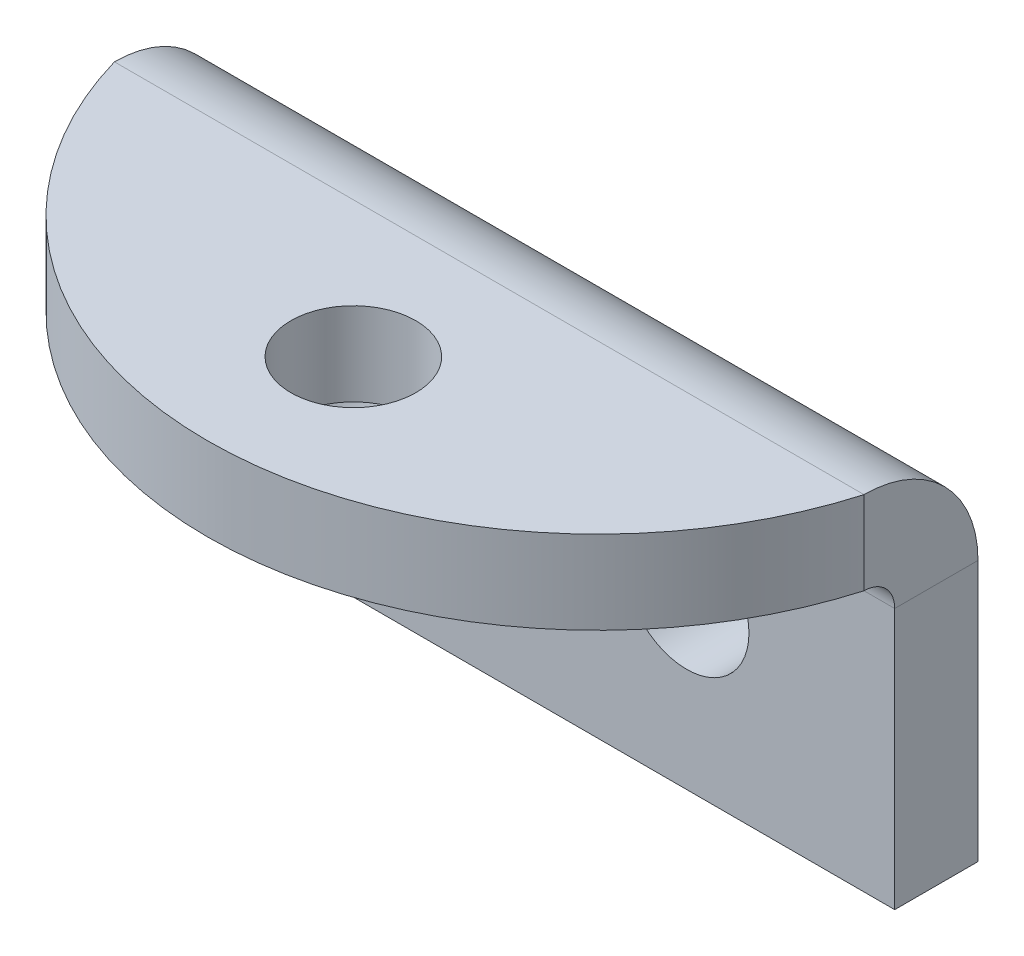
SolidWorks part; units mm, degrees
note: The reader was unsure of these and kept them because the rebuilt part matched: flange length of "边线-法兰1".
material "普通碳钢"
ref_plane "前视" through (0, 0, 0) normal (0, 0, 1) x (1, 0, 0)
ref_plane "上视" through (0, 0, 0) normal (0, 1, 0) x (1, 0, 0)
ref_plane "右视" through (0, 0, 0) normal (1, 0, 0) x (0, 0, -1)
sketch "草图1" plane through (0, 0, 0) normal (0, 0, 1) x (1, 0, 0)
  line L0 (9, 0) -> (9, -9) construction
  line L1 (0, 0) -> (18, 0)
  line L2 (0, 0) -> (0, -9)
  line L3 (0, -9) -> (18, -9)
  line L4 (18, 0) -> (18, -9)
  circle A0 centre (5, -5) radius 1.5
  circle A1 centre (13, -5) radius 1.5
  dimension "D3" = 8
  dimension "D4" = 4
  dimension "D5" = 3
  dimension "D1" = 18
  dimension "D2" = 9
base flange "基体-法兰1" sketch "草图1" thickness 2 reverse thickness direction no parameters "D1"=0.7366
edge flange "边线-法兰1" sketch "草图8" flange angle 90 flange length 20 flange position material inside bend radius 0.7366 thickness 2 relief rectangular parameters "D6"=10
sketch "草图8" plane through (0, 0, 0) normal (0, 1, 0) x (-1, 0, 0)
  line L0 (-18, 0) -> (0, 0) construction
  line L1 (-18, 0) -> (0, 0)
  line L2 (-18, 0) -> (-18, 18)
  line L3 (-18, 18) -> (0, 18)
  line L4 (0, 18) -> (0, 0)
bend "边线折弯1" bend radius 0.7366 bend angle 90 parameters "D5"=1
sketch "草图9" plane through (0, -2, 0) normal (0, -1, 0) x (1, 0, 0)
  line L0 (0, 0.7366) -> (0, 18) construction
  line L1 (18, 18) -> (18, 0.7366) construction
  line L5 (0, -2) -> (18, -2) construction
  line L6 (9, 7.5) -> (9, -2) construction
  line L7 (18, 0.7366) -> (0, 0.7366) construction
  line L8 (18, 0.7366) -> (18, 18)
  line L9 (18, 18) -> (0, 18)
  line L10 (0, 18) -> (0, 0.7366)
  arc A0 (0, 0.7366) -> (18, 0.7366) centre (9, -1.8698) cw
  circle A1 centre (9, 4) radius 1.5
  dimension "D1" = 9.5
  dimension "D2" = 3
  dimension "D3" = 6
extrude "切除-拉伸1" cut sketch "草图9" against normal blind 10 normal cut yes
sketch "折弯-线1" plane through (0, 0, 0) normal (0, 1, 0) x (1, 0, 0)
sketch "边界框1" plane through (0, 0, 0) normal (0, 1, 0) x (1, 0, 0)
sheet metal parameters "钣金4" thickness 2 parameters "D1"=0.7366
flat pattern "平板型式4" [suppressed]
sketch "折弯-线2" plane through (0, 0, 0) normal (0, 1, 0) x (1, 0, 0)
sketch "边界框2" [suppressed] plane through (0, 0, 0) normal (0, 1, 0) x (1, 0, 0)
sheet metal parameters "钣金5" thickness 2 parameters "D1"=0.7366
flat pattern "平板型式4" [suppressed]
sketch "折弯-线2" plane through (0, 0, 0) normal (0, 1, 0) x (1, 0, 0)
sketch "边界框2" [suppressed] plane through (0, 0, 0) normal (0, 1, 0) x (1, 0, 0)
bend of the flat pattern "展开-<边线折弯1>1"
sheet metal parameters "钣金6" thickness 2 parameters "D1"=0.7366
flat pattern "平板型式4" [suppressed]
sketch "折弯-线2" plane through (0, 0, 0) normal (0, 1, 0) x (1, 0, 0)
sketch "边界框2" [suppressed] plane through (0, 0, 0) normal (0, 1, 0) x (1, 0, 0)
bend of the flat pattern "展开-<边线折弯1>1"
